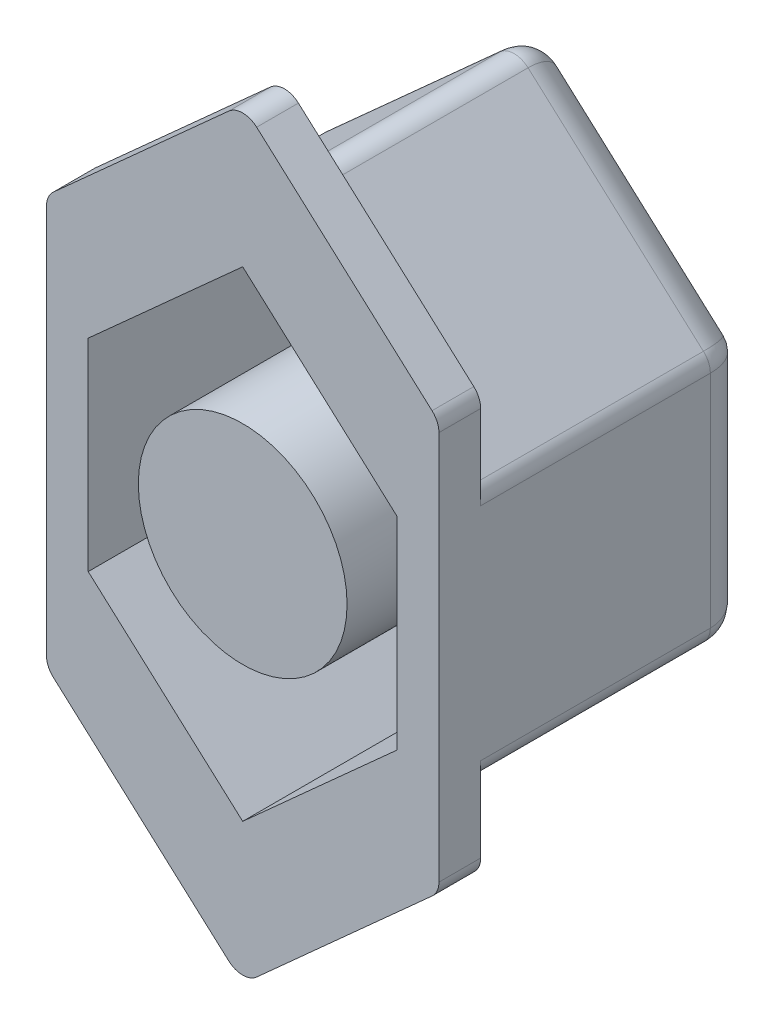
SolidWorks part; units mm, degrees
ref_plane "Front Plane" through (0, 0, 0) normal (0, 0, 1) x (1, 0, 0)
ref_plane "Top Plane" through (0, 0, 0) normal (0, 1, 0) x (1, 0, 0)
ref_plane "Right Plane" through (0, 0, 0) normal (1, 0, 0) x (0, 0, -1)
sketch "Sketch1" plane through (0, 0, 0) normal (0, 0, 1) x (1, 0, 0)
  line L0 (5, -10.5) -> (5, -4.5) construction
  line L1 (5, -4.5) -> (0, 0) construction
  line L2 (0, 0) -> (-5, -4.5) construction
  line L3 (-5, -4.5) -> (-5, -10.5) construction
  line L4 (-5, -10.5) -> (0, -15) construction
  line L5 (0, -15) -> (5, -10.5) construction
  line L6 (0, -0.4036) -> (-4.7, -4.6336)
  line L7 (-4.7, -4.6336) -> (-4.7, -10.3664)
  line L8 (-4.7, -10.3664) -> (0, -14.5964)
  line L9 (0, -14.5964) -> (4.7, -10.3664)
  line L10 (4.7, -10.3664) -> (4.7, -4.6336)
  line L11 (4.7, -4.6336) -> (0, -0.4036)
  dimension "D1" = 6
  dimension "D2" = 15
  dimension "D3" = 10
  dimension "D4" = 0.3
extrude "Boss-Extrude1" add sketch "Sketch1" along normal blind 7.5
sketch "Sketch2" plane through (0, 0, 7.5) normal (0, 0, 1) x (1, 0, 0)
  line L18 (0, 1.6144) -> (-4.7, -2.6156)
  line L20 (-4.7, -12.3844) -> (0, -16.6144)
  line L21 (0, -16.6144) -> (4.7, -12.3844)
  line L23 (4.7, -2.6156) -> (0, 1.6144)
  line L30 (4.7, -4.6336) -> (0, -0.4036)
  line L31 (0, -0.4036) -> (-4.7, -4.6336)
  line L32 (-4.7, -4.6336) -> (-4.7, -10.3664)
  line L33 (-4.7, -10.3664) -> (0, -14.5964)
  line L34 (0, -14.5964) -> (4.7, -10.3664)
  line L35 (4.7, -10.3664) -> (4.7, -4.6336)
  line L36 (4.7, -4.6336) -> (0, -0.4036)
  line L37 (0, -0.4036) -> (-4.7, -4.6336)
  line L39 (-4.7, -10.3664) -> (0, -14.5964)
  line L40 (0, -14.5964) -> (4.7, -10.3664)
  line L42 (-4.7, -4.6336) -> (-4.7, -2.6156)
  line L43 (-4.7, -10.3664) -> (-4.7, -12.3844)
  line L44 (4.7, -10.3664) -> (4.7, -12.3844)
  line L45 (4.7, -4.6336) -> (4.7, -2.6156)
  line L46 (0, 1.6144) -> (-6.2, -3.9656) construction
  line L47 (-6.2, -3.9656) -> (-6.2, -11.0344) construction
  line L48 (-6.2, -11.0344) -> (0, -16.6144) construction
  line L49 (0, -16.6144) -> (6.2, -11.0344) construction
  line L50 (6.2, -11.0344) -> (6.2, -3.9656) construction
  line L51 (6.2, -3.9656) -> (0, 1.6144) construction
  line L52 (4.7, -10.3664) -> (4.7, -4.6336) construction
  line L53 (-4.7, -4.6336) -> (-4.7, -10.3664) construction
  dimension "D2" = 1.5
  dimension "D1" = 0
extrude "Boss-Extrude2" add sketch "Sketch2" against normal blind 1
sketch "Sketch3" plane through (0, 0, 7.5) normal (0, 0, 1) x (1, 0, 0)
  line L28 (3.7, -5.079) -> (0, -1.749)
  line L29 (3.7, -9.921) -> (3.7, -5.079)
  line L30 (0, -13.251) -> (3.7, -9.921)
  line L31 (-3.7, -9.921) -> (0, -13.251)
  line L32 (-3.7, -5.079) -> (-3.7, -9.921)
  line L33 (0, -1.749) -> (-3.7, -5.079)
  line L34 (3.7, -5.079) -> (0, -1.749)
  line L35 (3.7, -9.921) -> (3.7, -5.079)
  line L36 (0, -13.251) -> (3.7, -9.921)
  line L37 (-3.7, -9.921) -> (0, -13.251)
  line L38 (-3.7, -5.079) -> (-3.7, -9.921)
  line L39 (0, -1.749) -> (-3.7, -5.079)
  dimension "D1" = 1
extrude "Cut-Extrude2" cut sketch "Sketch3" against normal blind 6.5
sketch "Sketch6" plane through (0, 0, 1) normal (0, 0, 1) x (1, 0, 0)
  line L1 (3.7, -9.921) -> (3.7, -5.079) construction
  line L2 (0, -7.5) -> (3.7, -7.5) construction
  line L3 (0, -7.5) -> (0, -13.251) construction
  line L4 (0, -13.251) -> (3.7, -9.921) construction
  line L5 (0, -13.251) -> (3.7, -9.921) construction
  circle A0 centre (0, -7.5) radius 2.5
  dimension "D1" = 5
extrude "Boss-Extrude5" add sketch "Sketch6" along normal blind 6.5 contours A0
fillet "Fillet1" radius 0.5 12 edges at (0, -14.5964, 3.25) (-4.7, -10.3664, 3.25) (-4.7, -4.6336, 3.25) (0, -0.4036, 3.25) (4.7, -10.3664, 3.25) (4.7, -4.6336, 3.25) (4.7, -12.3844, 7) (0, -16.6144, 7) (-4.7, -12.3844, 7) (-4.7, -2.6156, 7) (0, 1.6144, 7) (4.7, -2.6156, 7)
fillet "Fillet2" radius 1 12 edges at (4.6568, -10.3471, 0) (4.7, -7.5, 0) (4.6568, -4.6529, 0) (2.4345, -2.5946, 0) (0, -0.5763, 0) (-2.4345, -2.5946, 0) (-4.6568, -4.6529, 0) (-4.7, -7.5, 0) (-4.6568, -10.3471, 0) (-2.4345, -12.4054, 0) (0, -14.4237, 0) (2.4345, -12.4054, 0)
